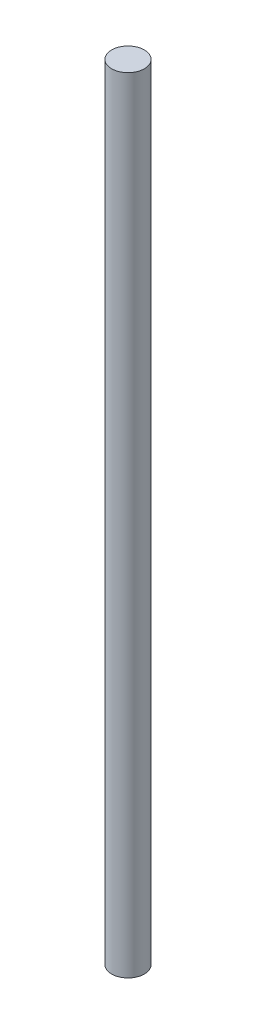
SolidWorks part; units mm, degrees
material "4140 Alloy Steel"
ref_plane "Front Plane" through (0, 0, 0) normal (0, 0, 1) x (1, 0, 0)
ref_plane "Top Plane" through (0, 0, 0) normal (0, 1, 0) x (1, 0, 0)
ref_plane "Right Plane" through (0, 0, 0) normal (1, 0, 0) x (0, 0, -1)
sketch "Sketch1" plane through (0, 0, 0) normal (0, 1, 0) x (1, 0, 0)
  circle A0 centre (0, 0) radius 6.35
  dimension "D1" = 12.7
extrude "Boss-Extrude1" add sketch "Sketch1" along normal blind 304.8
